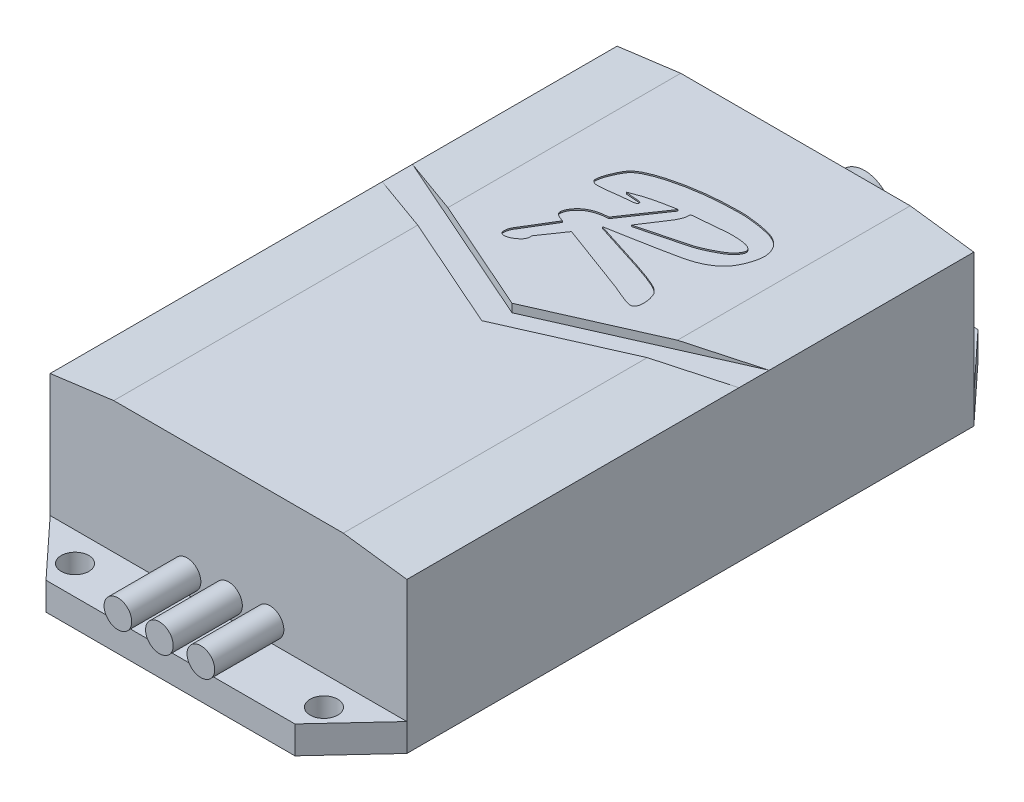
SolidWorks part; units mm, degrees
ref_plane "前视基准面" through (0, 0, 0) normal (0, 0, 1) x (1, 0, 0)
ref_plane "上视基准面" through (0, 0, 0) normal (0, 1, 0) x (1, 0, 0)
ref_plane "右视基准面" through (0, 0, 0) normal (1, 0, 0) x (0, 0, -1)
sketch "草图1" plane through (0, 0, 0) normal (0, 1, 0) x (1, 0, 0)
  line L0 (-12.9, 20.5) -> (-9, 24.7)
  line L1 (-9, 24.7) -> (9, 24.7)
  line L2 (-12.9, 20.5) -> (-12.9, -20.5)
  line L3 (-9, -24.7) -> (9, -24.7)
  line L4 (12.9, 20.5) -> (12.9, -20.5)
  line L5 (0, -24.7) -> (0, 24.7) construction
  line L6 (-12.9, 0) -> (12.9, 0) construction
  line L7 (-12.9, -20.5) -> (12.9, -20.5)
  line L8 (-12.9, -20.5) -> (-12.9, 20.5)
  line L9 (-12.9, 20.5) -> (12.9, 20.5)
  line L10 (12.9, -20.5) -> (12.9, 20.5)
  line L11 (0, 20.5) -> (0, -20.5) construction
  line L12 (-12.9, 0) -> (12.9, 0) construction
  line L13 (12.9, 20.5) -> (9, 24.7)
  line L14 (12.9, -20.5) -> (9, -24.7)
  line L15 (-12.9, -20.5) -> (-9, -24.7)
  point P0 (0, 0)
  point P4 (0, 0)
  dimension "D1" = 49.4
  dimension "D2" = 25.8
  dimension "D3" = 41
  dimension "D4" = 18
extrude "凸台-拉伸1" add sketch "草图1" along normal blind 11.5 contours L9 L2 L7 L4 region at (0, 0, 0)
extrude "凸台-拉伸2" add sketch "草图1<3>" along normal blind 2 contours L9 L13 L1 L0 | L7 L15 L3 L14 region at (0, 0, -22.4753) region at (0, 0, 22.4753)
sketch "草图1<3>" plane through (0, 0, 0) normal (0, 1, 0) x (1, 0, 0) same geometry as "草图1"
sketch "草图2" plane through (0, 2, 0) normal (0, 1, 0) x (1, 0, 0)
  line L0 (0, 33.0341) -> (0, -12.2052) construction
  line L1 (-21.4718, 0) -> (31.3074, 0) construction
  circle A0 centre (9, 22.6) radius 1
  circle A1 centre (9, -22.6) radius 1
  circle A2 centre (-9, -22.6) radius 1
  circle A3 centre (-9, 22.6) radius 1
  dimension "D1" = 2
  dimension "D2" = 9
  dimension "D3" = 22.6
extrude "切除-拉伸1" cut sketch "草图2" against normal through all
sketch "草图4" plane through (0, 0, 20.5) normal (0, 0, 1) x (1, 0, 0)
  line L0 (-12.9, 10.9) -> (-8.3, 11.5)
  line L1 (-12.9, 11.5) -> (-12.9, 2) construction
  line L2 (-12.9, 11.5) -> (12.9, 11.5) construction
  line L3 (0, 13.0304) -> (0, -3.5251) construction
  line L4 (-12.9, 10.9) -> (-12.9, 11.5)
  line L5 (-12.9, 11.5) -> (-8.3, 11.5)
  line L6 (12.9, 11.5) -> (8.3, 11.5)
  line L7 (12.9, 10.9) -> (12.9, 11.5)
  line L8 (12.9, 10.9) -> (8.3, 11.5)
  dimension "D1" = 0.6
  dimension "D2" = 4.6
extrude "切除-拉伸2" cut sketch "草图4" against normal through all
sketch "草图5" plane through (0, 0, 20.5) normal (0, 0, 1) x (1, 0, 0)
  line L0 (0, 14.8485) -> (0, -5.3415) construction
  line L1 (-9, 0) -> (9, 0) construction
  circle A0 centre (0, 3.3) radius 1
  circle A1 centre (3, 3.3) radius 1
  circle A2 centre (-3, 3.3) radius 1
  dimension "D1" = 2
  dimension "D2" = 2
  dimension "D3" = 2
  dimension "D4" = 3
  dimension "D5" = 3
  dimension "D6" = 3.3
  dimension "D7" = 3.3
  dimension "D8" = 3.3
extrude "凸台-拉伸3" add sketch "草图5" along normal blind 5
sketch "草图6" plane through (0, 0, -20.5) normal (0, 0, -1) x (-1, 0, 0)
  line L0 (9, 0) -> (-9, 0) construction
  circle A0 centre (0, 5) radius 2.5
  dimension "D1" = 5
  dimension "D2" = 5
extrude "凸台-拉伸4" add sketch "草图6" along normal blind 5 draft 5
sketch "草图7" plane through (0, 11.5, 0) normal (0, 1, 0) x (1, 0, 0)
  line L0 (-12.9, 5.7) -> (0, 0)
  line L1 (-12.9, 20.5) -> (-12.9, -20.5) construction
  line L2 (0, 0) -> (12.9, 5.7)
  line L3 (12.9, 20.5) -> (12.9, -20.5) construction
  line L4 (-12.9, 3.5135) -> (0, -2.1865)
  line L5 (0, -2.1865) -> (12.9, 3.5135)
  line L6 (-13.7083, 3.8706) -> (0, -2.1865) construction
  line L7 (0, -2.1865) -> (13.7083, 3.8706) construction
  line L8 (-12.9, 5.7) -> (-12.9, 3.5135)
  line L9 (12.9, 5.7) -> (12.9, 3.5135)
  dimension "D1" = 2
  dimension "D2" = 5.7
extrude "切除-拉伸3" cut sketch "草图7" against normal blind 0.6
sketch "草图8" plane through (0, 11.5, 0) normal (0, 1, 0) x (1, 0, 0)
  text T0 "R" font "Brush Script Std" height 10
extrude "切除-拉伸4" cut sketch "草图8" against normal blind 0.1
